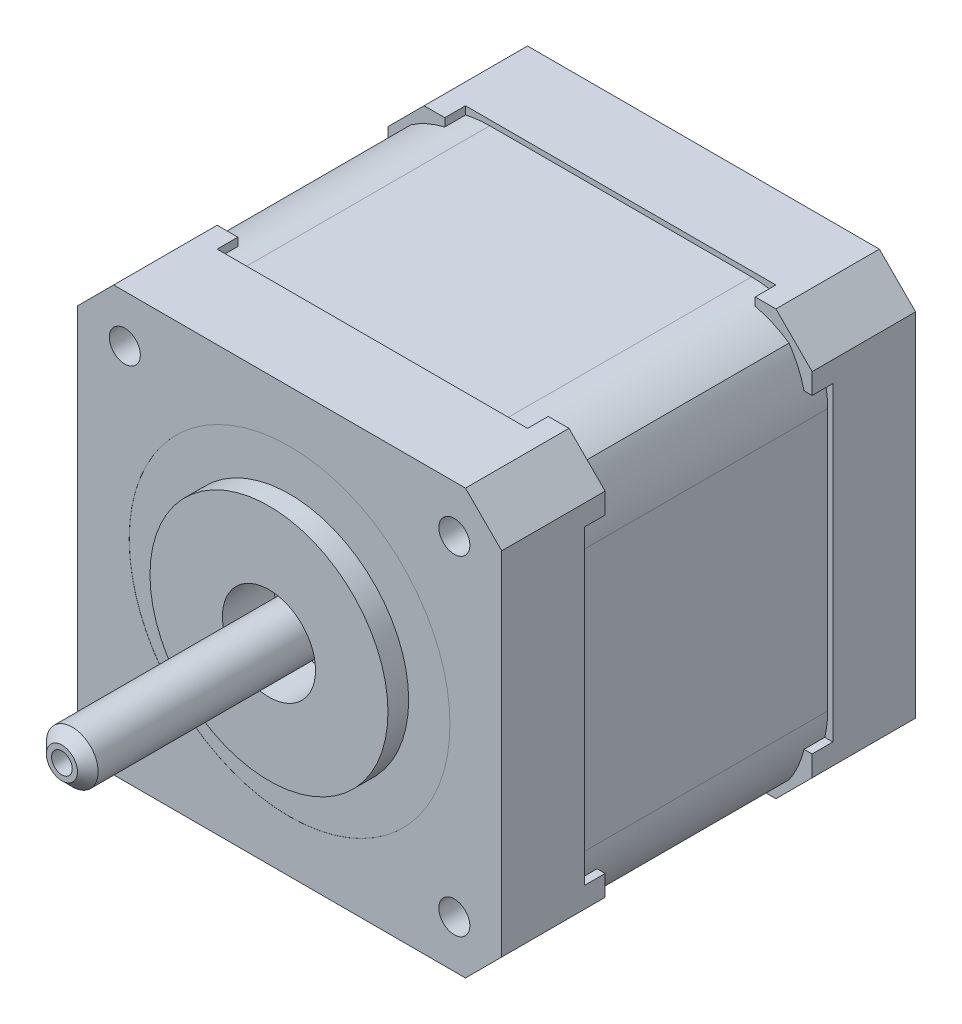
SolidWorks part; units mm, degrees
ref_plane "Ön Düzlem" through (0, 0, 0) normal (0, 0, 1) x (1, 0, 0)
ref_plane "Üst Düzlem" through (0, 0, 0) normal (0, 1, 0) x (1, 0, 0)
ref_plane "Sağ Düzlem" through (0, 0, 0) normal (1, 0, 0) x (0, 0, -1)
sketch "Çizim1" plane through (0, 0, 0) normal (0, 0, 1) x (1, 0, 0)
  line L3 (-17, 41) -> (17, 41)
  line L4 (20.5, 3.5) -> (20.5, 37.5)
  line L5 (-20.5, 3.5) -> (-20.5, 37.5)
  line L6 (17, 41) -> (20.5, 37.5)
  line L7 (-17, 41) -> (-20.5, 37.5)
  line L8 (17, 0) -> (20.5, 3.5)
  line L9 (-17, 0) -> (-20.5, 3.5)
  line L10 (-17, 0) -> (17, 0)
extrude "Yükseklik-Ekstrüzyon2" add sketch "Çizim1" along normal blind 8
sketch "Çizim5" plane through (0, 0, 0) normal (0, 0, -1) x (-1, 0, 0)
  line L0 (-20.5, 3.5) -> (-20.5, 5.5)
  line L1 (-20.5, 3.5) -> (-20.5, 37.5) construction
  line L2 (-20.5, 5.5) -> (-20, 5.5)
  line L3 (-17, 0) -> (-15, 0)
  line L4 (17, 0) -> (-17, 0) construction
  line L5 (-15, 0) -> (-15, 0.5)
  line L6 (20.5, 20.5) -> (10.3627, 20.5)
  line L7 (15, 0) -> (15, 0.5)
  line L8 (-20, 3.7071) -> (-20, 37.2929)
  line L9 (-20, 37.2929) -> (-16.7929, 40.5)
  line L10 (-16.7929, 40.5) -> (16.7929, 40.5)
  line L11 (16.7929, 40.5) -> (20, 37.2929)
  line L12 (20, 37.2929) -> (20, 3.7071)
  line L13 (20, 3.7071) -> (16.7929, 0.5)
  line L14 (16.7929, 0.5) -> (-16.7929, 0.5)
  line L15 (-16.7929, 0.5) -> (-20, 3.7071)
  line L16 (17, 0) -> (15, 0)
  line L17 (20.5, 5.5) -> (20, 5.5)
  line L18 (20.5, 3.5) -> (20.5, 5.5)
  line L19 (20.5, 37.5) -> (20.5, 3.5) construction
  line L20 (-20.5, 35.5) -> (-20, 35.5)
  line L21 (-15, 41) -> (-15, 40.5)
  line L22 (15, 41) -> (15, 40.5)
  line L23 (20.5, 37.5) -> (20.5, 35.5)
  line L24 (20.5, 35.5) -> (20, 35.5)
  line M4 (20.5, 37.5) -> (17, 41)
  line M5 (17, 41) -> (-17, 41)
  line M6 (-17, 41) -> (-20.5, 37.5)
  line M7 (-20.5, 37.5) -> (-20.5, 3.5)
  line M8 (-20.5, 3.5) -> (-17, 0)
  line M9 (-17, 0) -> (17, 0)
  line M10 (17, 0) -> (20.5, 3.5)
  line M11 (20.5, 3.5) -> (20.5, 37.5)
extrude "Yükseklik-Ekstrüzyon10" add sketch "Çizim5" along normal blind 2 contours L21 L20 L8 L9 L10 M5 M6 M7 | L24 L22 L10 L11 L12 M11 M4 M5 | L17 L12 L13 L14 L7 M11 M9 M10 | L14 L15 L8 L2 L5 M7 M8 M9 region at (20.4222, 4.5, 0) region at (20.4222, 36.5, 0) region at (-15.0778, 0.25, 0) region at (-16, 40.9222, 0)
sketch "Çizim12" plane through (0, 0, 0) normal (0, 0, -1) x (-1, 0, 0)
  line L1 (-20.5, 5.5) -> (-20.5, 3.5)
  line L2 (-20.5, 3.5) -> (-17, 0)
  line L3 (-17, 0) -> (17, 0)
  line L4 (17, 0) -> (20.5, 3.5)
  line L5 (20.5, 3.5) -> (20.5, 37.5)
  line L6 (20.5, 37.5) -> (17, 41)
  line L7 (17, 41) -> (-17, 41)
  line L8 (-17, 41) -> (-20.5, 37.5)
  line L9 (-20.5, 37.5) -> (-20.5, 35.5)
  line L10 (-20.5, 35.5) -> (-20.4853, 35.5072)
  line L11 (-20, 35.5) -> (-20, 5.5)
  line L12 (-20, 5.5) -> (-20, 3.7071)
  line L13 (-20, 3.7071) -> (-16.7929, 0.5)
  line L14 (-16.7929, 0.5) -> (16.7929, 0.5)
  line L15 (16.7929, 0.5) -> (20, 3.7071)
  line L16 (20, 3.7071) -> (20, 37.2929)
  line L17 (20, 37.2929) -> (16.7929, 40.5)
  line L18 (16.7929, 40.5) -> (-16.7929, 40.5)
  line L19 (-16.7929, 40.5) -> (-20, 37.2929)
  line L20 (-20, 37.2929) -> (-20, 35.5)
  line L21 (-20.5, 35.5) -> (-20.5, 5.5) construction
  line M3 (-20, 5.5) -> (-20, 3.7071)
  line M4 (-20, 3.7071) -> (-16.7929, 0.5)
  line M5 (-16.7929, 0.5) -> (-15, 0.5)
  line M9 (15, 0.5) -> (16.7929, 0.5)
  line M10 (16.7929, 0.5) -> (20, 3.7071)
  line M11 (20, 3.7071) -> (20, 5.5)
  line M15 (20, 35.5) -> (20, 37.2929)
  line M16 (20, 37.2929) -> (16.7929, 40.5)
  line M17 (16.7929, 40.5) -> (15, 40.5)
  line M21 (-15, 40.5) -> (-16.7929, 40.5)
  line M22 (-16.7929, 40.5) -> (-20, 37.2929)
  line M23 (-20, 37.2929) -> (-20, 35.5)
  dimension "D1" = 0.5
extrude "Yükseklik-Ekstrüzyon11" add sketch "Çizim12" along normal blind 24 contours L18 L11 L14 L16 M17 M21 M22 M23 M3 M4 M5 M9 M10 M11 M15 M16 region at (0, 20.5, 0)
sketch "Çizim13" plane through (0, 0, -24) normal (0, 0, -1) x (-1, 0, 0)
  line L0 (-17, 41) -> (-20.5, 37.5)
  line L1 (-20.5, 37.5) -> (-20.5, 3.5)
  line L2 (-20.5, 3.5) -> (-17, 0)
  line L3 (-17, 0) -> (17, 0)
  line L4 (17, 0) -> (20.5, 3.5)
  line L5 (20.5, 3.5) -> (20.5, 37.5)
  line L6 (20.5, 37.5) -> (17, 41)
  line L7 (17, 41) -> (-17, 41)
extrude "Yükseklik-Ekstrüzyon12" add sketch "Çizim13" along normal blind 8
sketch "Çizim14" plane through (0, 0, -24) normal (0, 0, 1) x (1, 0, 0)
  line L0 (17, 41) -> (15, 41)
  line L1 (-17, 41) -> (17, 41) construction
  line L2 (15, 41) -> (15, 40.5)
  line L3 (-16.7929, 40.5) -> (16.7929, 40.5) construction
  line L4 (15, 40.5) -> (16.7929, 40.5)
  line L5 (16.7929, 40.5) -> (20, 37.2929)
  line L6 (20.5, 37.5) -> (20.5, 35.5)
  line L7 (20.5, 37.5) -> (20.5, 3.5) construction
  line L8 (20.5, 35.5) -> (20, 35.5)
  line L9 (20, 37.2929) -> (20, 3.7071) construction
  line L10 (20, 35.5) -> (20, 37.2929)
  line L11 (20.5, 37.5) -> (17, 41)
  line L12 (0, 0) -> (0, 15.5815)
  line L13 (17, 0) -> (15, 0)
  line L14 (15, 0) -> (15, 0.5)
  line L15 (15, 0.5) -> (16.7929, 0.5)
  line L16 (20.5, 3.5) -> (17, 0)
  line L17 (16.7929, 0.5) -> (20, 3.7071)
  line L18 (20, 5.5) -> (20, 3.7071)
  line L19 (20.5, 3.5) -> (20.5, 5.5)
  line L20 (20.5, 5.5) -> (20, 5.5)
  line L21 (-20.5, 5.5) -> (-20, 5.5)
  line L22 (-20.5, 3.5) -> (-20.5, 5.5)
  line L23 (-20, 5.5) -> (-20, 3.7071)
  line L24 (-20.5, 3.5) -> (-17, 0)
  line L25 (-16.7929, 0.5) -> (-20, 3.7071)
  line L26 (-15, 0.5) -> (-16.7929, 0.5)
  line L27 (-15, 0) -> (-15, 0.5)
  line L28 (-17, 0) -> (-15, 0)
  line L29 (-20.5, 35.5) -> (-20, 35.5)
  line L30 (-20, 35.5) -> (-20, 37.2929)
  line L31 (-20.5, 37.5) -> (-20.5, 35.5)
  line L32 (-20.5, 37.5) -> (-17, 41)
  line L33 (-16.7929, 40.5) -> (-20, 37.2929)
  line L34 (-15, 40.5) -> (-16.7929, 40.5)
  line L35 (-17, 41) -> (-15, 41)
  line L36 (-15, 41) -> (-15, 40.5)
  line M19 (17, 41) -> (-17, 41)
  line M20 (-17, 41) -> (-20.5, 37.5)
  line M21 (-20.5, 37.5) -> (-20.5, 3.5)
  line M22 (-20.5, 3.5) -> (-17, 0)
  line M23 (-17, 0) -> (17, 0)
  line M24 (17, 0) -> (20.5, 3.5)
  line M25 (20.5, 3.5) -> (20.5, 37.5)
  line M26 (20.5, 37.5) -> (17, 41)
  line M27 (20, 37.2929) -> (20, 3.7071)
  line M28 (20, 3.7071) -> (16.7929, 0.5)
  line M29 (16.7929, 0.5) -> (-16.7929, 0.5)
  line M30 (-16.7929, 0.5) -> (-20, 3.7071)
  line M31 (-20, 3.7071) -> (-20, 37.2929)
  line M32 (-20, 37.2929) -> (-16.7929, 40.5)
  line M33 (-16.7929, 40.5) -> (16.7929, 40.5)
  line M34 (16.7929, 40.5) -> (20, 37.2929)
extrude "Yükseklik-Ekstrüzyon14" add sketch "Çizim14" along normal blind 2 contours L36 L29 M19 M20 M21 M31 M32 M33 | L27 L21 M23 M29 M30 M31 M21 M22 | L20 L14 M25 M27 M28 M29 M23 M24 | L8 L2 M25 M26 M19 M33 M34 M27 region at (18.695, 39.195, -24) region at (-15.0778, 40.75, -24) region at (20.4222, 4.5, -24) region at (-20.25, 5.4222, -24)
fillet "Radyus5" radius 10 8 edges at (-16.7929, 0.5, -12) (-20, 3.7071, -12) (-20, 37.2929, -12) (-16.7929, 40.5, -12) (16.7929, 40.5, -12) (20, 37.2929, -12) (20, 3.7071, -12) (16.7929, 0.5, -12)
sketch "Çizim15" plane through (0, 0, -32) normal (0, 0, -1) x (-1, 0, 0)
  circle A0 centre (0, 20.5) radius 4.5
extrude "Kes-Ekstrüzyon3" cut sketch "Çizim15" against normal blind 3
fillet "Radyus6" radius 0.5 1 edges at (-4.5, 20.5, -32)
sketch "Çizim16" plane through (0, 0, -29) normal (0, 0, -1) x (-1, 0, 0)
  circle A0 centre (0, 20.5) radius 3
extrude "Yükseklik-Ekstrüzyon15" add sketch "Çizim16" along normal blind 1
fillet "Radyus7" radius 0.5 1 edges at (-3, 20.5, -30)
sketch "Çizim17" plane through (0, 0, -30) normal (0, 0, -1) x (-1, 0, 0)
  line L1 (1.2603, 19.7965) -> (1.2394, 21.2397)
  line L2 (1.2394, 21.2397) -> (-0.0209, 21.9432)
  line L3 (-0.0209, 21.9432) -> (-1.2603, 21.2035)
  line L4 (-1.2603, 21.2035) -> (-1.2394, 19.7603)
  line L5 (-1.2394, 19.7603) -> (0.0209, 19.0568)
  line L6 (0.0209, 19.0568) -> (1.2603, 19.7965)
  circle A0 centre (0, 20.5) radius 1.25 construction
extrude "Kes-Ekstrüzyon4" cut sketch "Çizim17" against normal blind 0.5
sketch "Çizim18" plane through (0, 0, -32) normal (0, 0, -1) x (-1, 0, 0)
  line L0 (0, 20.5) -> (0, 35.5)
  line L1 (0, 20.5) -> (15, 20.5)
  line L2 (0, 35.5) -> (15, 35.5)
  line L3 (15, 35.5) -> (15, 20.5)
  circle A0 centre (15, 35.5) radius 3
  circle A1 centre (15, 5.5) radius 3
  circle A2 centre (-15, 5.5) radius 3
  circle A3 centre (-15, 35.5) radius 3
extrude "Kes-Ekstrüzyon5" cut sketch "Çizim18" against normal blind 1 contours A2 | A0 | A1 | A3 region at (15, 5.5, -32)
sketch "Çizim19" plane through (0, 0, -31) normal (0, 0, -1) x (-1, 0, 0)
  circle A0 centre (15, 35.5) radius 2
  circle A1 centre (15, 5.5) radius 2
  circle A2 centre (-15, 5.5) radius 2
  circle A3 centre (-15, 35.5) radius 2
extrude "Yükseklik-Ekstrüzyon17" add sketch "Çizim19" along normal blind 0.5
fillet "Radyus8" radius 0.5 4 edges at (13, 5.5, -31.5) (-13, 5.5, -31.5) (-17, 35.5, -31.5) (17, 35.5, -31.5)
sketch "Çizim21" plane through (0, 0, -31.5) normal (0, 0, -1) x (-1, 0, 0)
  line L0 (0, 20.5) -> (9.2525, 20.5)
  line L1 (9.2525, 20.5) -> (0, 20.5)
  line L2 (0, 20.5) -> (0, 30.2455)
  line L3 (15.15, 6.5) -> (14.85, 6.5)
  line L4 (15.15, 35.65) -> (15.15, 36.5)
  line L5 (15.15, 35.35) -> (16, 35.35)
  line L6 (14.85, 35.35) -> (14.85, 34.5)
  line L7 (14.85, 35.65) -> (14, 35.65)
  line L8 (14.85, 35.65) -> (14.85, 36.5)
  line L9 (15.15, 35.65) -> (16, 35.65)
  line L10 (15.15, 35.35) -> (15.15, 34.5)
  line L11 (14.85, 35.35) -> (14, 35.35)
  line L12 (14.85, 36.5) -> (15.15, 36.5)
  line L13 (16, 35.65) -> (16, 35.35)
  line L14 (15.15, 34.5) -> (14.85, 34.5)
  line L15 (14, 35.35) -> (14, 35.65)
  line L16 (14, 35.65) -> (14.0342, 35.6422)
  line L17 (14, 5.35) -> (14.0342, 5.3578)
  line L18 (14, 5.65) -> (14, 5.35)
  line L19 (16, 5.35) -> (16, 5.65)
  line L20 (14.85, 5.65) -> (14, 5.65)
  line L21 (15.15, 5.65) -> (15.15, 6.5)
  line L22 (15.15, 5.35) -> (16, 5.35)
  line L23 (14.85, 5.35) -> (14, 5.35)
  line L24 (14.85, 5.65) -> (14.85, 6.5)
  line L25 (15.15, 5.65) -> (16, 5.65)
  line L26 (14.85, 4.5) -> (15.15, 4.5)
  line L27 (14.85, 5.35) -> (14.85, 4.5)
  line L28 (15.15, 5.35) -> (15.15, 4.5)
  line L29 (-14, 35.65) -> (-14.0342, 35.6422)
  line L30 (-14, 35.35) -> (-14, 35.65)
  line L31 (-14.85, 36.5) -> (-15.15, 36.5)
  line L32 (-15.15, 34.5) -> (-14.85, 34.5)
  line L33 (-16, 35.65) -> (-16, 35.35)
  line L34 (-14.85, 35.35) -> (-14, 35.35)
  line L35 (-15.15, 35.35) -> (-15.15, 34.5)
  line L36 (-15.15, 35.65) -> (-16, 35.65)
  line L37 (-14.85, 35.65) -> (-14.85, 36.5)
  line L38 (-14.85, 35.65) -> (-14, 35.65)
  line L39 (-14.85, 35.35) -> (-14.85, 34.5)
  line L40 (-15.15, 35.35) -> (-16, 35.35)
  line L41 (-15.15, 35.65) -> (-15.15, 36.5)
  line L42 (-16, 5.35) -> (-16, 5.65)
  line L43 (-15.15, 5.35) -> (-15.15, 4.5)
  line L44 (-14.85, 5.35) -> (-14.85, 4.5)
  line L45 (-14.85, 4.5) -> (-15.15, 4.5)
  line L46 (-15.15, 5.65) -> (-16, 5.65)
  line L47 (-14.85, 5.65) -> (-14.85, 6.5)
  line L48 (-14.85, 5.35) -> (-14, 5.35)
  line L49 (-15.15, 5.35) -> (-16, 5.35)
  line L50 (-15.15, 5.65) -> (-15.15, 6.5)
  line L51 (-14.85, 5.65) -> (-14, 5.65)
  line L52 (-14, 5.65) -> (-14, 5.35)
  line L53 (-14, 5.35) -> (-14.0342, 5.3578)
  line L54 (-15.15, 6.5) -> (-14.85, 6.5)
  point P0 (15, 35.5)
  point P1 (15, 36.5)
  point P3 (15.15, 35.5)
  point P4 (16, 35.5)
  point P5 (15, 34.5)
  point P10 (14.85, 35.5)
  point P14 (14.85, 35.5)
extrude "Kes-Ekstrüzyon6" cut sketch "Çizim21" against normal blind 0.1 contours L41 L36 L33 L40 L35 L32 L39 L34 L30 L38 L37 L31 | L15 L11 L6 L14 L10 L5 L13 L9 L4 L12 L8 L7 | L28 L22 L19 L25 L21 L3 L24 L20 L18 L23 L27 L26 | L54 L50 L46 L42 L49 L43 L45 L44 L48 L52 L51 L47 region at (-15, 5.5, -31.5) region at (-15, 35.5, -31.5) region at (15, 35.5, -31.5) region at (15, 5.5, -31.5)
sketch "Çizim22" plane through (0, 0, 8) normal (0, 0, 1) x (1, 0, 0)
  circle A0 centre (0, 20.5) radius 4.5
extrude "Kes-Ekstrüzyon7" cut sketch "Çizim22" against normal blind 3
sketch "Çizim23" plane through (0, 0, 5) normal (0, 0, 1) x (1, 0, 0)
  circle A0 centre (0, 20.5) radius 2.5
extrude "Yükseklik-Ekstrüzyon18" add sketch "Çizim23" along normal blind 25
sketch "Çizim24" plane through (0, 0, 30) normal (0, 0, 1) x (1, 0, 0)
  circle A0 centre (0, 20.5) radius 1
extrude "Kes-Ekstrüzyon8" cut sketch "Çizim24" against normal blind 2
chamfer "Pah1" distance 1 angle 45 1 edges at (2.5, 20.5, 30)
sketch "Çizim25" plane through (0, 0, 8) normal (0, 0, 1) x (1, 0, 0)
  line L0 (20.5, 20.5) -> (15.5, 20.5)
  line L1 (20.5, 3.5) -> (20.5, 37.5) construction
  circle A0 centre (0, 20.5) radius 4.5
  circle A1 centre (0, 20.5) radius 15.5
  circle M2 centre (0, 20.5) radius 4.5
extrude "Kes-Ekstrüzyon9" cut sketch "Çizim25" against normal blind 0.01 contours A1 M2 region at (-15.0616, 20.5, 8)
sketch "Çizim26" plane through (0, 0, 7.99) normal (0, 0, 1) x (1, 0, 0)
  line L0 (15.5, 20.5) -> (11.5, 20.5)
  circle A0 centre (0, 20.5) radius 4.5
  circle A1 centre (0, 20.5) radius 15.5 construction
  circle A2 centre (0, 20.5) radius 11.5
  circle M2 centre (0, 20.5) radius 4.5
extrude "Yükseklik-Ekstrüzyon19" add sketch "Çizim26" along normal blind 2 contours A2 M2 region at (-11.1747, 20.5, 7.99)
sketch "Çizim28" plane through (0, 0, 8) normal (0, 0, 1) x (1, 0, 0)
  line L2 (0, 20.5) -> (0, 27.7903)
  line L3 (0, 27.7903) -> (0, 20.5)
  line L4 (0, 20.5) -> (6.5303, 20.5)
  circle A0 centre (-15.9216, 36.4216) radius 1.5
  circle A1 centre (15.9216, 36.4216) radius 1.5
  circle A2 centre (-15.9216, 4.5784) radius 1.5
  circle A3 centre (15.9216, 4.5784) radius 1.5
extrude "Kes-Ekstrüzyon10" cut sketch "Çizim28" against normal blind 6 contours A1 | A0 | A3 | A2 region at (-15.9216, 36.4216, 8) region at (15.9216, 36.4216, 8) region at (-15.9216, 4.5784, 8) region at (15.9216, 4.5784, 8)
